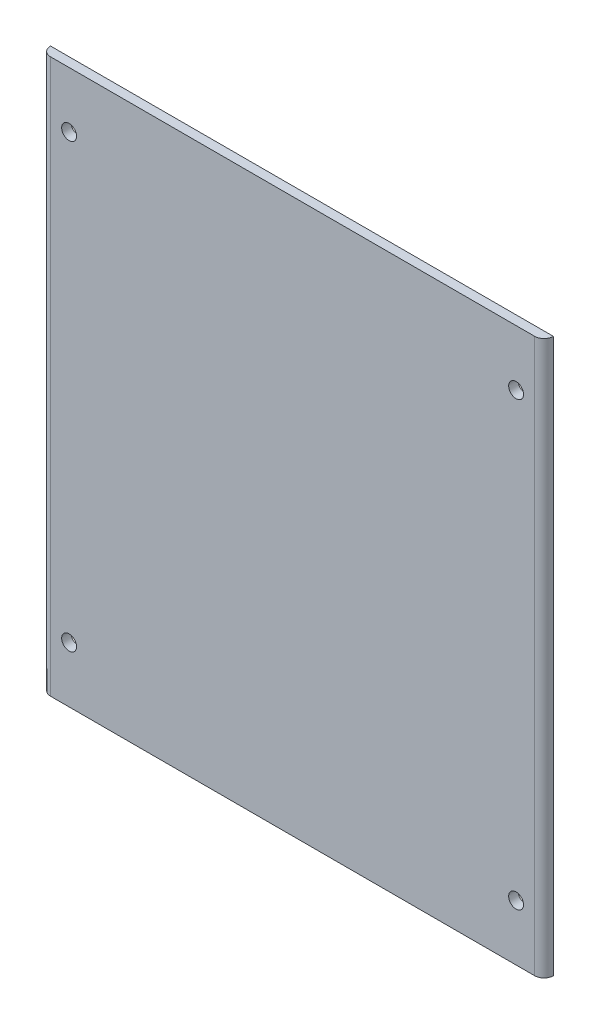
SolidWorks part; units mm, degrees
ref_plane "Płaszczyzna przednia" through (0, 0, 0) normal (0, 0, 1) x (1, 0, 0)
ref_plane "Płaszczyzna górna" through (0, 0, 0) normal (0, 1, 0) x (1, 0, 0)
ref_plane "Płaszczyzna prawa" through (0, 0, 0) normal (1, 0, 0) x (0, 0, -1)
sketch "Szkic1" plane through (0, 0, 0) normal (0, 0, 1) x (1, 0, 0)
  line L1 (-4, 0) -> (-108, 0)
  line L2 (-4, 0) -> (-4, 118.94)
  line L3 (-4, 118.94) -> (-108, 118.94)
  line L4 (-108, 0) -> (-108, 118.94)
extrude "Dodanie-wyciągnięcie1" add sketch "Szkic1" along normal blind 2
sketch "Szkic2" plane through (0, 0, 0) normal (0, 0, -1) x (-1, 0, 0)
  line L0 (110, 116.94) -> (108, 118.94)
  line L1 (108, 0) -> (110, 0)
  line L2 (108, 0) -> (108, 116.94)
  line L3 (108, 116.94) -> (110, 116.94)
  line L4 (110, 0) -> (110, 116.94)
  line L5 (108, 118.94) -> (108, 116.94)
  line L6 (2, 116.94) -> (4, 118.94)
  line L7 (4, 0) -> (2, 0)
  line L8 (4, 0) -> (4, 116.94)
  line L9 (4, 116.94) -> (2, 116.94)
  line L10 (2, 0) -> (2, 116.94)
  line L11 (4, 118.94) -> (4, 116.94)
  line L13 (4, 118.94) -> (2, 118.94)
  line L14 (4, 118.94) -> (4, 116.94)
  line L15 (4, 116.94) -> (2, 116.94)
  line L16 (2, 118.94) -> (2, 116.94)
  line L17 (108, 118.94) -> (110, 118.94)
  line L18 (108, 118.94) -> (108, 116.94)
  line L19 (108, 116.94) -> (110, 116.94)
  line L20 (110, 118.94) -> (110, 116.94)
extrude "Dodanie-wyciągnięcie2" add sketch "Szkic2" against normal blind 2 contours L10 L7 L4 L9 | L9 L4 L6 | L1 L4 L3 L2 | L2 L3 L0 | L14 L13 L16 L15 | L18 L17 L20 L19 region at (-108.6667, 117.6067, 0) region at (-109, 58.47, 0) region at (-3.3333, 117.6067, 0) region at (-3, 58.47, 0)
sketch "Szkic3" plane through (0, 0, 2) normal (0, 0, 1) x (1, 0, 0)
  line L0 (-108, 118.94) -> (-108, 102.94) construction
  line L1 (-4, 118.94) -> (-4, 102.94) construction
  line L2 (-4, 102.94) -> (-12, 102.94) construction
  line L3 (-108, 102.94) -> (-100, 102.94) construction
  line L4 (-108, 0) -> (-108, 16) construction
  line L5 (-4, 0) -> (-4, 16) construction
  line L6 (-4, 16) -> (-12, 16) construction
  line L7 (-108, 16) -> (-100, 16) construction
  line L8 (-100, 16) -> (-100, 8) construction
  line L9 (-100, 8) -> (-108, 16) construction
  line L10 (-12, 16) -> (-12, 8) construction
  line L11 (-12, 8) -> (-4, 16) construction
  line L12 (-100, 102.94) -> (-100, 110.94) construction
  line L13 (-100, 110.94) -> (-108, 102.94) construction
  line L14 (-12, 102.94) -> (-12, 110.94) construction
  line L15 (-12, 110.94) -> (-4, 102.94) construction
  circle A0 centre (-104, 12) radius 1.6
  circle A1 centre (-8, 12) radius 1.6
  circle A2 centre (-8, 106.94) radius 1.6
  circle A3 centre (-104, 106.94) radius 1.6
extrude "Wytnij-wyciągnięcie1" cut sketch "Szkic3" against normal blind 2
fillet "Zaokrąglenie1" radius 2 2 edges at (-2, 59.47, 2) (-110, 59.47, 2)
